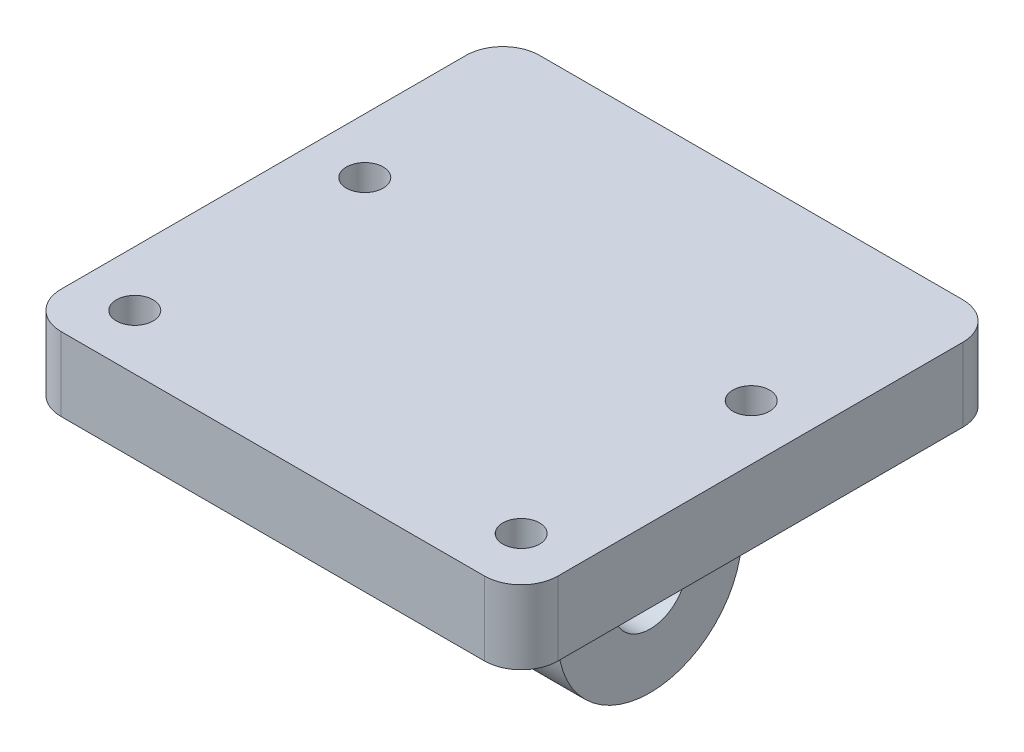
SolidWorks part; units mm, degrees
ref_plane "Front Plane" through (0, 0, 0) normal (0, 0, 1) x (1, 0, 0)
ref_plane "Top Plane" through (0, 0, 0) normal (0, 1, 0) x (1, 0, 0)
ref_plane "Right Plane" through (0, 0, 0) normal (1, 0, 0) x (0, 0, -1)
sketch "Sketch1" plane through (0, 0, 0) normal (0, 1, 0) x (1, 0, 0)
  line L0 (13.5, -13) -> (13.5, 13)
  line L5 (12.5, -12) -> (-12.5, 12) construction
  line L6 (12.5, 12) -> (-12.5, -12) construction
  line L7 (10.5, -10) -> (-10.5, -10) construction
  line L8 (10.5, -10) -> (10.5, 2.5) construction
  line L9 (10.5, 2.5) -> (-10.5, 2.5) construction
  line L10 (-10.5, -10) -> (-10.5, 2.5) construction
  line L11 (10.5, -10) -> (-10.5, 2.5) construction
  line L12 (10.5, 2.5) -> (-10.5, -10) construction
  line L13 (13.5, 13) -> (-13.5, 13)
  line L14 (-13.5, -13) -> (-13.5, 13)
  line L15 (13.5, -13) -> (-13.5, -13)
  circle A0 centre (-10.5, 2.5) radius 1
  circle A1 centre (-10.5, -10) radius 1
  circle A2 centre (10.5, -10) radius 1
  circle A3 centre (10.5, 2.5) radius 1
  point P0 (0, 0)
  point P6 (0, -3.75)
  dimension "D1" = 25
  dimension "D2" = 24
  dimension "D3" = 12.5
  dimension "D4" = 21
extrude "Boss-Extrude1" add sketch "Sketch1" along normal blind 4
sketch "Sketch2" plane through (0, 0, 0) normal (0, -1, 0) x (1, 0, 0)
  line L1 (7.5, -5) -> (-7.5, -5)
  line L2 (7.5, -5) -> (7.5, 5)
  line L3 (7.5, 5) -> (-7.5, 5)
  line L4 (-7.5, -5) -> (-7.5, 5)
  line L5 (7.5, -5) -> (-7.5, 5) construction
  line L6 (7.5, 5) -> (-7.5, -5) construction
  line L7 (-2.5, 5) -> (2.5, 5)
  line L8 (-2.5, 5) -> (-2.5, -5)
  line L9 (-2.5, -5) -> (2.5, -5)
  line L10 (2.5, 5) -> (2.5, -5)
  point P0 (0, 0)
  dimension "D1" = 15
  dimension "D2" = 10
  dimension "D3" = 5
  dimension "D4" = 5
extrude "Boss-Extrude2" add sketch "Sketch2" along normal blind 10 contours L8 L3 L4 L1 | L3 L10 L1 L2 region at (5, 0, 0) region at (-5, 0, 0)
fillet "Fillet1" radius 5 4 edges at (5, -10, 5) (5, -10, -5) (-5, -10, 5) (-5, -10, -5)
sketch "Sketch4" plane through (-7.5, 0, 0) normal (-1, 0, 0) x (0, 0, 1)
  line L0 (-5, 0) -> (5, 0) construction
  circle A0 centre (0, -5) radius 2
  dimension "D1" = 5
extrude "Cut-Extrude1" cut sketch "Sketch4" against normal blind 22 and the other way blind 11
fillet "Fillet2" radius 2 4 edges at (13.5, 2, 13) (-13.5, 2, 13) (-13.5, 2, -13) (13.5, 2, -13)
